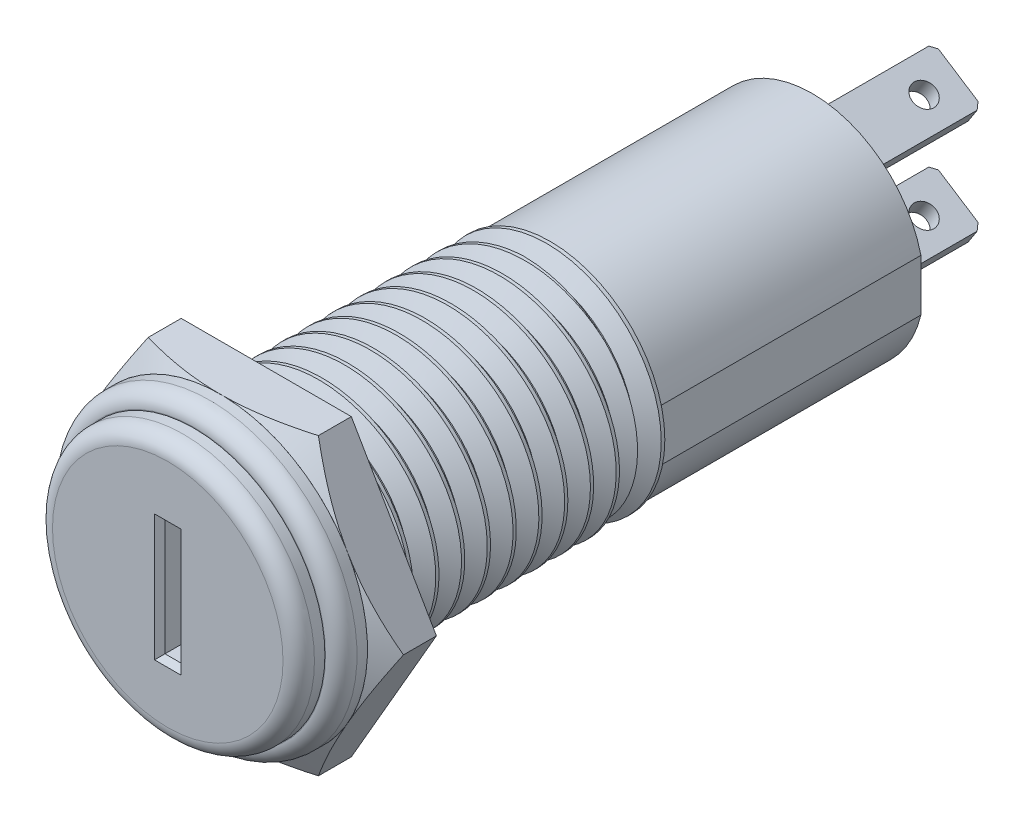
SolidWorks part; units mm, degrees
ref_plane "Front" through (0, 0, 0) normal (0, 0, 1) x (1, 0, 0)
ref_plane "Top" through (0, 0, 0) normal (0, 1, 0) x (1, 0, 0)
ref_plane "Right" through (0, 0, 0) normal (1, 0, 0) x (0, 0, -1)
sketch "Sketch1" plane through (0, 0, 0) normal (1, 0, 0) x (0, 0, -1)
  line L0 (-19.05, 0) -> (19.05, 0) construction
  line L1 (0, 5.5562) -> (0, -5.5562) construction
  line L2 (14.2748, 7.1437) -> (14.2748, -7.1437) construction
  point P5 (14.2748, 0)
  point P6 (-12.192, 0)
  point P9 (0, 0)
  dimension "D1" = 38.1
  dimension "Body Dia" = 11.1125
  dimension "Projection" = 4.7752
  dimension "Terminal Depth" = 6.858
  dimension "Diameter" = 14.2875
ref_plane "Plane1" through (0, 0, -19.05) normal (0, 0, 1) x (1, 0, 0)
sketch "Sketch2" plane through (0, 0, -19.05) normal (0, 0, 1) x (1, 0, 0)
  circle A0 centre (0, 0) radius 6.35
  dimension "D1" = 12.7
extrude "Boss-Extrude1" add sketch "Sketch2" along normal blind 1.27
sketch "Sketch3" plane through (0, 0, -17.78) normal (0, 0, 1) x (1, 0, 0)
  circle A0 centre (0, 0) radius 7.1438
extrude "Boss-Extrude2" add sketch "Sketch3" along normal blind 1.27 separate body
sketch "Sketch4" plane through (0, 0, -16.51) normal (0, 0, 1) x (1, 0, 0)
  line L1 (4.1244, -7.1437) -> (8.2489, 0)
  line L2 (8.2489, 0) -> (4.1244, 7.1437)
  line L3 (4.1244, 7.1437) -> (-4.1244, 7.1437)
  line L4 (-4.1244, 7.1437) -> (-8.2489, 0)
  line L5 (-8.2489, 0) -> (-4.1244, -7.1438)
  line L6 (-4.1244, -7.1438) -> (4.1244, -7.1437)
  circle A0 centre (0, 0) radius 7.1438 construction
extrude "Boss-Extrude3" add sketch "Sketch4" along normal up to vertex (2.2352 mm away) separate body up to point (0, 0, -14.2748)
sketch "Sketch5" plane through (0, 0, -16.51) normal (0, 0, -1) x (-1, 0, 0)
  circle A0 centre (0, 0) radius 7.1438 construction
  circle A1 centre (0, 0) radius 7.1438
extrude "Cut-Extrude1" cut sketch "Sketch5" against normal blind 1.27 draft 60 flip side to cut
sketch "Sketch6" plane through (0, 0, -14.2748) normal (0, 0, 1) x (1, 0, 0)
  circle A0 centre (0, 0) radius 5.5562
extrude "Boss-Extrude4" add sketch "Sketch6" along normal up to vertex (26.4668 mm away) separate body up to point (0, 0, 12.192)
ref_plane "Plane2" through (0, 0, -14.2748) normal (0, 0, 1) x (1, 0, 0)
sketch "Sketch7" plane through (0, 0, -14.2748) normal (0, 0, 1) x (1, 0, 0)
  circle A0 centre (0, 0) radius 5.5562 construction
  circle A1 centre (0, 0) radius 5.5562
curve "Helix/Spiral1" pitch 1.25 height 12.5 turns 10
sketch "Sketch8" plane through (0, 0, 0) normal (1, 0, 0) x (0, 0, -1)
  line L0 (0.6029, 5.6916) -> (1.8529, 5.6916) construction
  line L1 (1.8529, 5.6916) -> (1.2279, 4.609) construction
  line L2 (1.2279, 4.609) -> (0.6029, 5.6916) construction
  line L3 (0.7592, 5.4209) -> (1.6967, 5.4209) construction
  line L4 (1.1498, 4.7444) -> (1.306, 4.7444) construction
  line L5 (1.2279, 5.4209) -> (1.2279, 5.5562) construction
  line L6 (1.2279, 5.5562) -> (1.2279, 5.6916) construction
  line L7 (1.2279, 4.7444) -> (1.2279, 4.609) construction
  line L8 (1.2279, 5.5562) -> (1.7748, 5.5562) construction
  line L9 (0.6029, 5.6916) -> (1.7748, 5.5562)
  line L10 (1.7748, 5.5562) -> (1.306, 4.7444)
  line L11 (1.306, 4.7444) -> (1.1498, 4.7444)
  line L12 (1.1498, 4.7444) -> (0.6029, 5.6916)
  dimension "D1" = 1.25
  dimension "D2" = 0.1562
sweep "Cut-Sweep1" cut profiles "Sketch8" path "Helix/Spiral1" align with end faces yes
ref_plane "Plane3" through (0, 5.5562, -1.7748) normal (0, 0, -1) x (-1, 0, 0)
sketch "Sketch11" plane through (0, 5.5562, -1.7748) normal (0, 0, -1) x (-1, 0, 0)
  circle A0 centre (0, -5.5562) radius 5.5563
  circle A1 centre (0, -5.5562) radius 5.5562 construction
sketch "Sketch12" plane through (0, 0, 0) normal (1, 0, 0) x (0, 0, -1)
  line L0 (1.7748, 5.5562) -> (1.306, 4.7444)
  line L1 (1.1498, 4.7444) -> (0.681, 5.5563)
  line L2 (0.681, 5.5563) -> (1.7748, 5.5562)
  line L3 (1.7748, 5.5562) -> (1.306, 4.7444) construction
  line L4 (1.1498, 4.7444) -> (1.306, 4.7444)
  line L5 (1.1498, 4.7444) -> (0.681, 5.5563) construction
sweep "Cut-Sweep2" cut profiles "Sketch12" path "Sketch11"
sketch "Sketch13" plane through (0, 0, 12.192) normal (0, 0, 1) x (1, 0, 0)
  line L0 (-5.5562, 0) -> (5.5562, 0) construction
  line L1 (0, 5.5562) -> (0, -5.5562) construction
  line L2 (0, 7.1437) -> (0, -7.1437) construction
  line L3 (0.9527, 3.6254) -> (-1.3939, 2.1087)
  line L4 (-1.3939, 2.1087) -> (-0.9527, 1.4261)
  line L5 (-0.9527, 1.4261) -> (1.3939, 2.9427)
  line L6 (1.3939, 2.9427) -> (0.9527, 3.6254)
  line L7 (-1.1733, 1.7674) -> (1.1733, 3.284) construction
  circle A0 centre (0, 0) radius 5.5562 construction
  point P13 (0.2206, 2.1844)
  point P14 (-0.2206, 2.867)
  point P17 (0, 2.5257)
  point P18 (0, -2.5257)
  dimension "D1" = 2.794
  dimension "D2" = 0.8128
  dimension "D3" = 122.876
  dimension "D4" = 2.5257
  dimension "D5" = 2.5257
extrude "Boss-Extrude5" add sketch "Sketch13" along normal up to vertex (6.858 mm away) separate body up to point (0, 0, 19.05)
sketch "Sketch14" plane through (-1.3721, 2.1228, 0) normal (-0.5428, 0.8398, 0) x (0.8398, 0.5428, 0)
  line L0 (1.371, -19.05) -> (1.371, -12.192) construction
  line L1 (2.768, -19.05) -> (-0.026, -19.05) construction
  line L3 (2.768, -12.192) -> (-0.026, -12.192) construction
  circle A0 centre (1.371, -17.3963) radius 0.5638
  dimension "D1" = 1.1275
  dimension "D2" = 1.6537
extrude "Cut-Extrude2" cut sketch "Sketch14" against normal up to next (0.8128 mm away)
chamfer "Chamfer1" distance 0.254 angle 45 2 edges at (1.1733, 3.284, 19.05) (-1.1733, 1.7674, 19.05)
pattern_linear "LPattern2" count 2 spacing 5.08 along (0, -1, 0) of bodies 117
sketch "Sketch15" plane through (0, 0, -19.05) normal (0, 0, -1) x (-1, 0, 0)
  line L1 (-0.3878, 2.8115) -> (0.3878, 2.8115)
  line L2 (-0.3878, 2.8115) -> (-0.3878, -2.8115)
  line L3 (-0.3878, -2.8115) -> (0.3878, -2.8115)
  line L4 (0.3878, 2.8115) -> (0.3878, -2.8115)
  line L5 (-0.3878, 2.8115) -> (0.3878, -2.8115) construction
  line L6 (-0.3878, -2.8115) -> (0.3878, 2.8115) construction
  point P0 (0, 0)
  dimension "D1" = 5.623
  dimension "D2" = 0.7756
extrude "Cut-Extrude3" cut sketch "Sketch15" against normal up to vertex (4.7752 mm away) up to point (0, 0, -14.2748)
chamfer "Chamfer2" distance 0.254 angle 45 4 edges at (0, -2.8115, -19.05) (-0.3878, 0, -19.05) (0, 2.8115, -19.05) (0.3878, 0, -19.05)
move or copy body "Body-Move/Copy1" bodies to move or copy 119 117 115 121 122 120 copy no rotation origin (-0.0204, 0, -3.5044) rotation axis (0, 1, 0) rotation angle 180
fillet "Fillet1" radius 0.762 1 edges at (-6.3908, 0, 12.0412)
fillet "Fillet2" radius 0.762 1 edges at (-7.1846, 0, 10.7712)
sketch "Sketch16" plane through (0, 0, -19.2008) normal (0, 0, -1) x (-1, 0, 0)
  line L0 (-8.2081, 0) -> (-4.0836, -7.1438) construction
  line L1 (-5.2297, 1.7589) -> (5.3113, 1.7589) construction
  line L2 (-5.2297, 1.7589) -> (-5.2297, -1.7589)
  line L3 (-5.2297, -1.7589) -> (5.3113, -1.7589) construction
  line L4 (5.3113, 1.7589) -> (5.3113, -1.7589)
  line L5 (-1.2598, 4.7665) -> (1.557, -5.5563) construction
  line L6 (-5.8814, -4.0299) -> (2.972, 1.9946) construction
  line L7 (-5.2297, 0) -> (5.3113, 0) construction
  line L8 (0.0408, 5.5562) -> (0.0408, -5.5562) construction
  circle A0 centre (0.0408, 0) radius 5.5563 construction
  arc A1 (-5.2297, -1.7589) -> (5.3113, -1.7589) centre (0.0408, 0) ccw
  arc A2 (5.3113, 1.7589) -> (-5.2297, 1.7589) centre (0.0408, 0) ccw
  point P7 (-2.5433, 4.9188)
  dimension "D1" = 10.541
extrude "Cut-Extrude4" cut sketch "Sketch16" against normal blind 12.7 flip side to cut
sketch "Sketch17" plane through (0, 0, -19.2008) normal (0, 0, -1) x (-1, 0, 0)
  circle A0 centre (0.0408, 0) radius 5.4174
  arc A1 (5.3113, 1.7589) -> (-5.2297, 1.7589) centre (0.0408, 0) ccw construction
  dimension "D1" = 10.8348
extrude "Cut-Extrude5" cut sketch "Sketch17" against normal up to vertex (12.7 mm away) flip side to cut up to point (5.2297, 1.7589, -6.5008)
equation "\"D2@Sketch8\"=\"D1@Sketch8\"/8"
equation "\"D1@Sketch8\"=\"D4@Helix/Spiral1\""
equation "\"D5@Sketch13\"=\"D4@Sketch13\""
